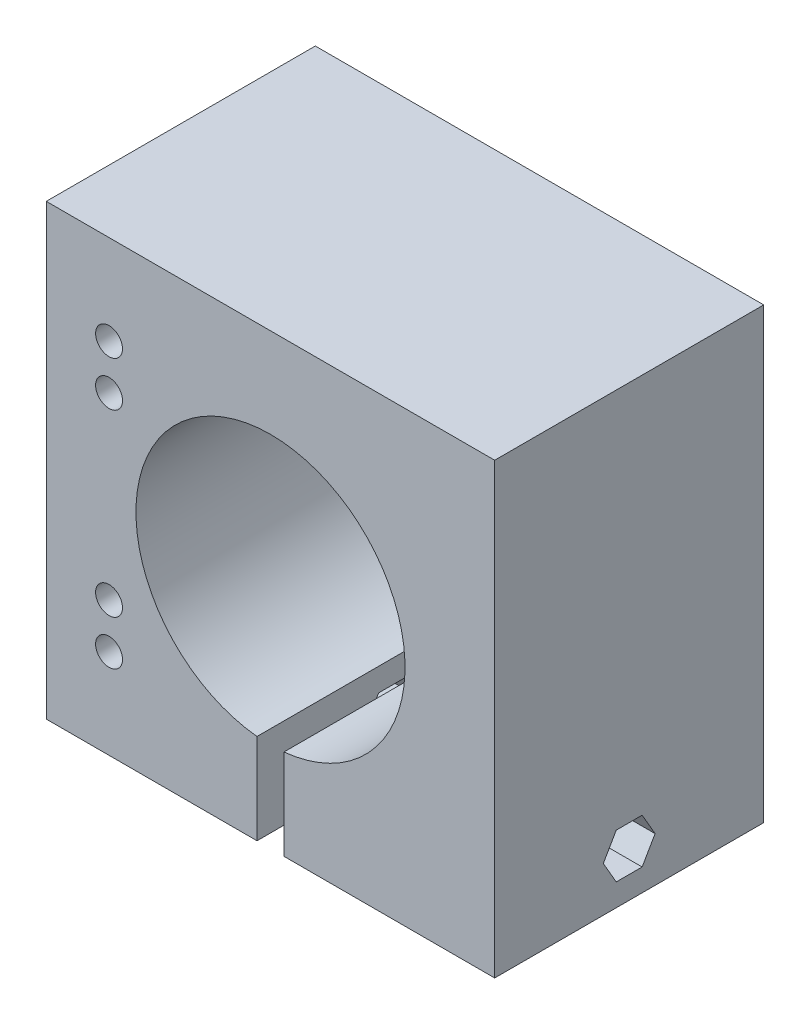
SolidWorks part; units mm, degrees
ref_plane "Front Plane" through (0, 0, 0) normal (0, 0, 1) x (1, 0, 0)
ref_plane "Top Plane" through (0, 0, 0) normal (0, 1, 0) x (1, 0, 0)
ref_plane "Right Plane" through (0, 0, 0) normal (1, 0, 0) x (0, 0, -1)
sketch "Sketch1" plane through (0, 0, 0) normal (0, 0, 1) x (1, 0, 0)
  line L1 (0, 0) -> (50, 0)
  line L2 (0, 0) -> (0, 50)
  line L3 (0, 50) -> (50, 50)
  line L4 (50, 0) -> (50, 50)
  circle A0 centre (25, 25) radius 15
  circle A1 centre (7, 15) radius 1.5
  circle A2 centre (7, 40) radius 1.5
  circle A3 centre (7, 10) radius 1.5
  circle A4 centre (7, 35) radius 1.5
  dimension "D3" = 30
  dimension "D6" = 5
  dimension "D7" = 3
  dimension "D14" = 18
  dimension "D8" = 3
  dimension "D1" = 50
  dimension "D2" = 50
  dimension "D4" = 25
  dimension "D5" = 25
  dimension "D9" = 5
  dimension "D11" = 10
  dimension "D12" = 10
  dimension "D13" = 18
extrude "Boss-Extrude1" add sketch "Sketch1" along normal blind 30
sketch "Sketch2" plane through (0, 0, 30) normal (0, 0, 1) x (1, 0, 0)
  line L0 (0, 0) -> (50, 0) construction
  line L1 (23.5, 0) -> (26.5, 0)
  line L2 (23.5, 0) -> (23.5, 11.7091)
  line L3 (23.5, 11.7091) -> (26.5, 11.7091)
  line L4 (26.5, 0) -> (26.5, 11.7091)
  line L5 (50, 0) -> (50, 50) construction
  dimension "D1" = 3
  dimension "D2" = 23.5
extrude "Cut-Extrude1" cut sketch "Sketch2" against normal up to next
sketch "Sketch3" plane through (50, 0, 0) normal (1, 0, 0) x (0, 0, -1)
  line L2 (-13.5566, 7.5) -> (-16.4434, 2.5) construction
  line L3 (-12.1132, 5) -> (-13.5566, 7.5)
  line L4 (-13.5566, 7.5) -> (-16.4434, 7.5)
  line L5 (-16.4434, 7.5) -> (-17.8868, 5)
  line L6 (-17.8868, 5) -> (-16.4434, 2.5)
  line L7 (-16.4434, 2.5) -> (-13.5566, 2.5)
  line L8 (-13.5566, 2.5) -> (-12.1132, 5)
  line L9 (0, 0) -> (0, 50) construction
  line L10 (-30, 0) -> (0, 0) construction
  point P0 (-15, 5)
  dimension "D1" = 15
  dimension "D2" = 5
  dimension "D4" = 5
extrude "Cut-Extrude2" cut sketch "Sketch3" against normal blind 54
sketch "Sketch4" plane through (0, 0, 0) normal (-1, 0, 0) x (0, 0, 1)
  line L1 (19.6188, 5) -> (17.3094, 9)
  line L2 (17.3094, 9) -> (12.6906, 9)
  line L3 (12.6906, 9) -> (10.3812, 5)
  line L4 (10.3812, 5) -> (12.6906, 1)
  line L5 (12.6906, 1) -> (17.3094, 1)
  line L6 (17.3094, 1) -> (19.6188, 5)
  dimension "D1" = 8
extrude "Cut-Extrude3" cut sketch "Sketch4" against normal blind 5
